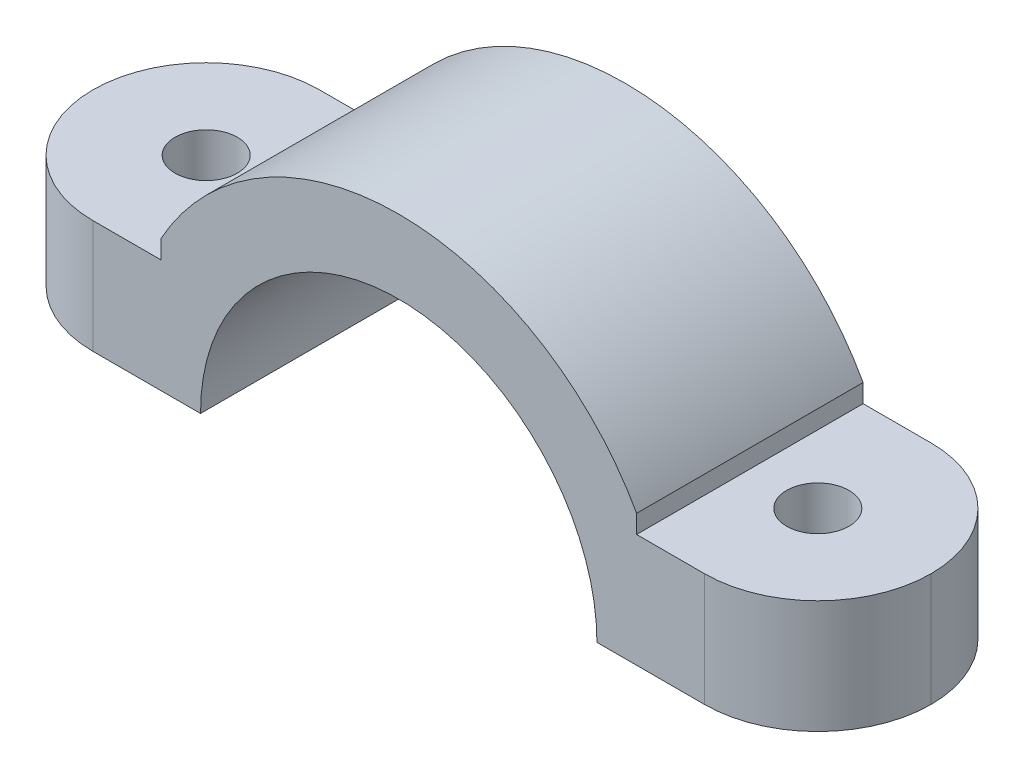
SolidWorks part; units mm, degrees
ref_plane "Front Plane" through (0, 0, 0) normal (0, 0, 1) x (1, 0, 0)
ref_plane "Top Plane" through (0, 0, 0) normal (0, 1, 0) x (1, 0, 0)
ref_plane "Right Plane" through (0, 0, 0) normal (1, 0, 0) x (0, 0, -1)
sketch "Sketch1" plane through (0, 0, 0) normal (0, 0, 1) x (1, 0, 0)
  line L0 (35, 0) -> (74, 0)
  line L1 (-74, 20) -> (-42, 20)
  line L2 (-74, 20) -> (-74, 0)
  line L3 (-74, 0) -> (-35, 0)
  line L4 (74, 20) -> (74, 0)
  line L5 (42, 20) -> (74, 20)
  line L6 (-102.9087, 0) -> (114.1694, 0) construction
  line L7 (-74, 0) -> (-74, 25.4953) construction
  line L8 (54, 25.4953) -> (74, 25.4953) construction
  line L9 (74, 25.4953) -> (74, 0) construction
  line L10 (54, 25.4953) -> (42, 25.4953) construction
  line L12 (42, 23.2379) -> (42, 20)
  line L15 (-74, 25.4953) -> (-54, 25.4953) construction
  line L16 (-54, 25.4953) -> (-42, 25.4953) construction
  line L21 (-42, 23.2379) -> (-42, 20)
  arc A0 (42, 23.2379) -> (-42, 23.2379) centre (0, 0) ccw
  arc A1 (35, 0) -> (-35, 0) centre (0, 0) ccw
  dimension "D1" = 96
  dimension "D2" = 70
  dimension "D3" = 20
  dimension "D4" = 74
  dimension "D5" = 74
  dimension "D6" = 20
  dimension "D7" = 12
  dimension "D8" = 20
  dimension "D9" = 12
extrude "Boss-Extrude1" add sketch "Sketch1" along normal blind 20 and the other way blind 20
sketch "Sketch7" plane through (0, 20, 0) normal (0, 1, 0) x (1, 0, 0)
  line L0 (0, -45.2664) -> (0, 45.2664) construction
  line L1 (-96.5999, 0) -> (96.5999, 0) construction
  circle A0 centre (54, 0) radius 5.5
  circle A2 centre (-54, 0) radius 5.5
extrude "Cut-Extrude5" cut sketch "Sketch7" against normal blind 20
fillet "Fillet8" radius 20 4 edges at (-74, 10, -20) (-74, 10, 20) (74, 10, -20) (74, 10, 20)
